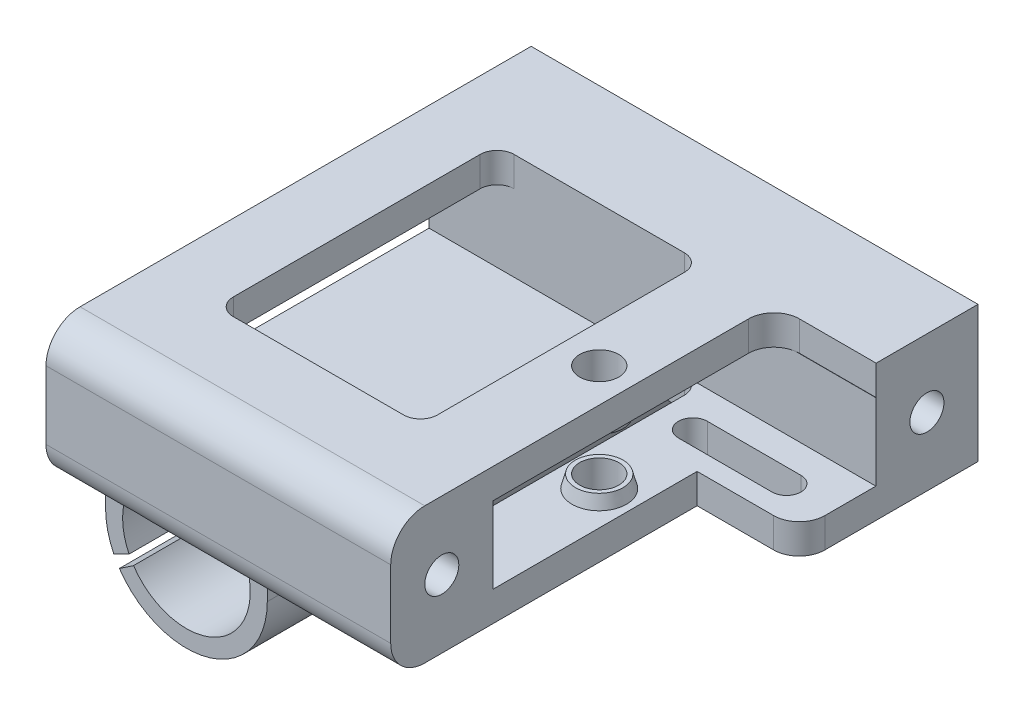
SolidWorks part; units mm, degrees
ref_plane "Front Plane" through (0, 0, 0) normal (0, 0, 1) x (1, 0, 0)
ref_plane "Top Plane" through (0, 0, 0) normal (0, 1, 0) x (1, 0, 0)
ref_plane "Right Plane" through (0, 0, 0) normal (1, 0, 0) x (0, 0, -1)
sketch "Sketch1" plane through (0, 0, 0) normal (0, 0, 1) x (1, 0, 0)
  line L0 (0, 0) -> (0, -31.5)
  line L1 (0, -31.5) -> (19, -31.5)
  line L2 (19, -31.5) -> (19, -16)
  line L3 (19, -16) -> (52.5, -16)
  line L4 (52.5, -16) -> (52.5, 0)
  line L5 (52.5, 0) -> (0, 0)
  line L6 (0, 0) -> (0.6966, -0.1385)
  dimension "D1" = 31.5
  dimension "D2" = 19
  dimension "D3" = 52.5
  dimension "D4" = 16
extrude "Boss-Extrude1" add sketch "Sketch1" along normal blind 57 contours L4 L5 L0 L1 L2 L3 region at (21.9019, -12.0885, 0)
ref_plane "Plane1" through (0, 0, 50) normal (0, 0, 1) x (1, 0, 0)
sketch "Sketch3" plane through (0, 0, 0) normal (-1, 0, 0) x (0, 0, 1)
  line L0 (57, 0) -> (0, 0) construction
  line L1 (12, -3.5) -> (45, -3.5)
  line L2 (12, -3.5) -> (12, -12.5)
  line L3 (12, -12.5) -> (45, -12.5)
  line L4 (45, -3.5) -> (45, -12.5)
  line L5 (57, -31.5) -> (50, -31.5)
  line L6 (57, -31.5) -> (57, -16)
  line L7 (57, -16) -> (50, -16)
  line L8 (50, -31.5) -> (50, -16)
  line L9 (0, 0) -> (0, -31.5) construction
  line L10 (50, -17.325) -> (50, 17.325) construction
  line L14 (57, -31.5) -> (0, -31.5) construction
  dimension "D1" = 9
  dimension "D2" = 33
  dimension "D3" = 3.5
  dimension "D4" = 12
  dimension "D5" = 15.5
  dimension "D6" = 7
extrude "Cut-Extrude2" cut sketch "Sketch3" against normal through all
fillet "Fillet1" radius 4 2 edges at (26.25, 0, 57) (26.25, -16, 57)
sketch "Sketch4" plane through (0, 0, 0) normal (0, 0, -1) x (-1, 0, 0)
  line L0 (-9.5, -22) -> (-9.5, -31.5) construction
  line L1 (0, -31.5) -> (-19, -31.5) construction
  line L2 (-2.759, -25.2878) -> (-0.9615, -26.1645)
  line L3 (0, -31.5) -> (-19, -31.5)
  line L4 (0, -31.5) -> (0, -16)
  line L5 (0, -16) -> (-19, -16)
  line L6 (-19, -31.5) -> (-19, -16)
  line L7 (-3.2822, -26.1939) -> (-1.6241, -27.3123)
  line L8 (-2.759, -25.2878) -> (-9.5, -22) construction
  circle A0 centre (-9.5, -22) radius 7.5
  circle A1 centre (-9.5, -22) radius 9.5
  line M8 (-19, -31.5) -> (0, -31.5)
  line M9 (0, -31.5) -> (0, 0)
  dimension "D1" = 15
  dimension "D2" = 19
  dimension "D3" = 8
  dimension "D4" = 64
extrude "Cut-Extrude3" cut sketch "Sketch4" against normal through all contours L5 A0 | L5 A0 | A1 L6 M8 | A1 L3 M9 | L7 A1 L2 A0 region at (2.1108, -26.2661, 0) region at (9.5, -22.3626, 0) region at (2.122, -29.378, 0) region at (9.5, -15.3945, 0) region at (16.878, -29.378, 0)
sketch "Sketch5" plane through (0, -16, 0) normal (0, -1, 0) x (1, 0, 0)
  line L0 (32, 28.5) -> (36, 28.5) construction
  line L1 (22, 45) -> (30, 45)
  line L2 (20, 43) -> (20, 14)
  line L3 (22, 12) -> (30, 12)
  line L4 (32, 43) -> (32, 14)
  line L5 (36, 17) -> (47, 17) construction
  line L6 (36, 18.7) -> (47, 18.7)
  line L7 (36, 15.3) -> (47, 15.3)
  line L8 (19, 50) -> (19, 0) construction
  line L9 (36, 28.5) -> (36, 17) construction
  line L10 (19, 0) -> (52.5, 0) construction
  line L11 (52.5, 0) -> (52.5, 18) construction
  line L12 (52.5, 53) -> (52.5, 0) construction
  line L14 (49.5, 18) -> (49.5, 21) construction
  line L15 (49.5, 21) -> (40.5, 21)
  line L16 (40.5, 21) -> (40.5, 57)
  line L17 (0, 57) -> (52.5, 57) construction
  line L18 (40.5, 57) -> (52.5, 57)
  line L19 (52.5, 57) -> (52.5, 18)
  arc A0 (20, 14) -> (22, 12) centre (22, 14) ccw
  arc A1 (30, 12) -> (32, 14) centre (30, 14) ccw
  arc A2 (32, 43) -> (30, 45) centre (30, 43) ccw
  arc A3 (22, 45) -> (20, 43) centre (22, 43) ccw
  circle A4 centre (36, 28.5) radius 2 construction
  arc A5 (36, 18.7) -> (36, 15.3) centre (36, 17) ccw
  arc A6 (47, 15.3) -> (47, 18.7) centre (47, 17) ccw
  arc A7 (52.5, 18) -> (49.5, 21) centre (49.5, 18) ccw
  point P17 (41.5, 17)
  line M7 (52.5, 53) -> (14, 53)
  line M12 (52.5, 0) -> (52.5, 53)
  dimension "D1" = 2
  dimension "D4" = 4
  dimension "D6" = 1.7
  dimension "D9" = 11.5
  dimension "D12" = 6
  dimension "D2" = 12
  dimension "D3" = 33
  dimension "D5" = 4
  dimension "D7" = 11
  dimension "D8" = 1
  dimension "D10" = 12
  dimension "D11" = 18
  dimension "D13" = 9
extrude "Cut-Extrude4" cut sketch "Sketch5" against normal up to surface (12.5 mm away) contours A4 | L7 A6 L6 A5 | A7 L16 L15 M12 M7 | L19 L18 L16 M7 | L2 A0 L3 A1 L4 A2 L1 A3 region at (41.5, -16, 17) region at (46.5267, -16, 36.9166) region at (46.5, -16, 55) up to face at (26.25, -3.5, 28.5)
sketch "Sketch6" plane through (0, 0, 0) normal (0, 1, 0) x (1, 0, 0)
  line L0 (52.5, 0) -> (0, 0) construction
  line L1 (10, -12) -> (30, -12)
  line L2 (8, -14) -> (8, -43)
  line L3 (10, -45) -> (30, -45)
  line L4 (32, -14) -> (32, -43)
  line L5 (0, -53) -> (0, 0) construction
  line L6 (52.5, -56.9686) -> (40.5, -56.9686) construction
  line L7 (43.5, -11.9686) -> (52.5, -11.9686)
  line L8 (40.5, -14.9686) -> (40.5, -56.9686)
  line L9 (40.5, -56.9686) -> (52.5, -56.9686)
  line L10 (52.5, -11.9686) -> (52.5, -56.9686)
  line L11 (52.5, -53) -> (52.5, 0) construction
  line L12 (36, -28.5) -> (32, -28.5) construction
  arc A0 (10, -45) -> (8, -43) centre (10, -43) cw
  arc A1 (32, -43) -> (30, -45) centre (30, -43) cw
  arc A2 (32, -14) -> (30, -12) centre (30, -14) ccw
  arc A3 (10, -12) -> (8, -14) centre (10, -14) ccw
  arc A4 (43.5, -11.9686) -> (40.5, -14.9686) centre (43.5, -14.9686) ccw
  circle A5 centre (36, -28.5) radius 2 construction
  point P6 (8, -45)
  point P11 (32, -12)
  point P14 (8, -12)
  point P25 (40.5, -11.9686)
  dimension "D3" = 2
  dimension "D8" = 3
  dimension "D9" = 4
  dimension "D10" = 4
  dimension "D1" = 33
  dimension "D2" = 24
  dimension "D4" = 12
  dimension "D5" = 8
  dimension "D6" = 45
  dimension "D7" = 12
extrude "Cut-Extrude5" cut sketch "Sketch6" against normal up to surface (3.5 mm away) up to face at (31, -3.5, 37.9895)
sketch "Sketch9" plane through (0, -3.5, 0) normal (0, -1, 0) x (1, 0, 0)
  line L0 (40.5, 21) -> (40.5, 53) construction
  line L1 (19, 0) -> (52.5, 0) construction
  circle A0 centre (36.5, 28.5) radius 3.2
  dimension "D1" = 6.4
  dimension "D2" = 4
  dimension "D3" = 28.5
ref_plane "Plane3" through (0, -5, 0) normal (0, -1, 0) x (-1, 0, 0)
sketch "Sketch10" plane through (0, -5, 0) normal (0, -1, 0) x (-1, 0, 0)
  circle A0 centre (-36.5, -28.5) radius 2.8
  dimension "D1" = 5.6
loft "Loft1" add profiles "Sketch9", "Sketch10" connector at (36.5, -3.5, 25.3) connector at (36.5, -5, 25.7)
ref_plane "Plane4" through (0, -8, 0) normal (0, -1, 0) x (-1, 0, 0)
mirror "Mirror2" about plane through (0, -8, 0) normal (0, -1, 0) of "Loft1"
sketch "Sketch11" plane through (0, -11, 0) normal (0, 1, 0) x (1, 0, 0)
  circle A0 centre (36.5, -28.5) radius 2.3
  dimension "D1" = 4.6
extrude "Cut-Extrude6" cut sketch "Sketch11" against normal through all both and the other way through all
sketch "Sketch13" plane through (52.5, 0, 0) normal (1, 0, 0) x (0, 0, -1)
  line L0 (-51, -8) -> (-6, -8) construction
  line L1 (-6, -8) -> (0, -8) construction
  line L2 (0, -16) -> (0, 0) construction
  line L3 (-51, -8) -> (-57, -8) construction
  line L5 (-57, -4) -> (-57, -12) construction
  circle A0 centre (-6, -8) radius 2
  circle A1 centre (-51, -8) radius 2
  dimension "D1" = 45
  dimension "D2" = 4
extrude "Cut-Extrude7" cut sketch "Sketch13" against normal blind 20
